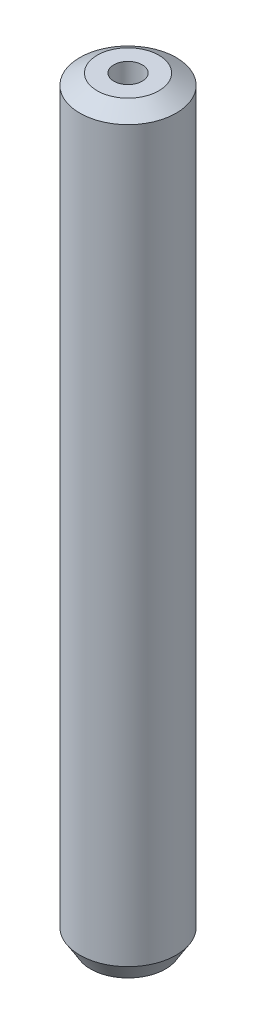
SolidWorks part; units mm, degrees
ref_plane "Front Plane" through (0, 0, 0) normal (0, 0, 1) x (1, 0, 0)
ref_plane "Top Plane" through (0, 0, 0) normal (0, 1, 0) x (1, 0, 0)
ref_plane "Right Plane" through (0, 0, 0) normal (1, 0, 0) x (0, 0, -1)
sketch "Sketch1" plane through (0, 0, 0) normal (0, 1, 0) x (1, 0, 0)
  circle A0 centre (0, 0) radius 12.5
  dimension "SHAFT_OD" = 25
extrude "Boss-Extrude1" add sketch "Sketch1" along normal blind 196.3556
sketch "Sketch2" plane through (0, 0, 0) normal (0, 1, 0) x (1, 0, 0)
  circle A0 centre (0, 0) radius 3.6907
  dimension "BORE_D" = 7.3814
extrude "Cut-Extrude1" cut sketch "Sketch2" along normal through all
chamfer "Chamfer1" distance 2.7689 angle 58.411 2 edges at (0, 196.3556, 12.5) (0, 0, 12.5) first distance on face at (0, 196.3556, 12.5) first distance on face at (0, 0, 3.6907)
